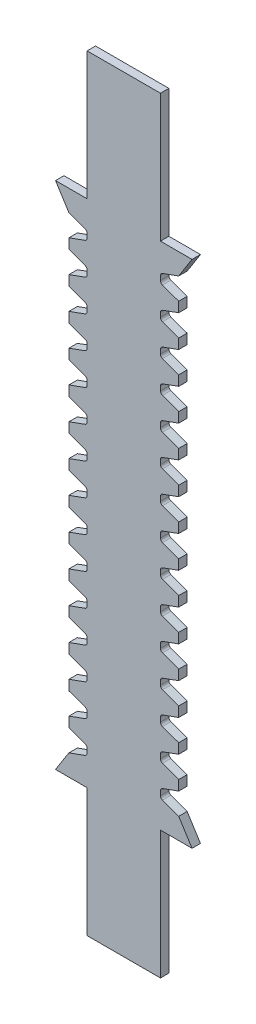
SolidWorks part; units mm, degrees
ref_plane "Front Plane" through (0, 0, 0) normal (0, 0, 1) x (1, 0, 0)
ref_plane "Top Plane" through (0, 0, 0) normal (0, 1, 0) x (1, 0, 0)
ref_plane "Right Plane" through (0, 0, 0) normal (1, 0, 0) x (0, 0, -1)
ref_axis "Axis1" through (0, -557.0644, 0) along (0, 1, 0)
sketch "SketchCI.m_strSketchName" plane through (0, 0, 0) normal (0, 0, 1) x (1, 0, 0)
  line L0 (-7.7057, 15.1301) -> (-7.7057, -438.7728)
  line L1 (-7.7057, -438.7728) -> (44.46, -438.7728)
  line L2 (44.46, -438.7728) -> (44.46, 15.1301)
  line L3 (44.46, 15.1301) -> (-7.7057, 15.1301)
  dimension "D1" = 7.7057
  dimension "D2" = 438.7728
  dimension "D3" = 44.46
  dimension "D4" = 15.1301
extrude "ExtrudeCI" add sketch "SketchCI.m_strSketchName" along normal blind 4 and the other way blind 4
sketch "SketchToothGeartrax1Gear" plane through (0, 0, 0) normal (0, 0, 1) x (1, 0, 0)
  line L0 (-7.7057, 10.3697) -> (-7.7057, -10.3697)
  line L1 (-7.7057, -10.3697) -> (7.7308, -4.7513)
  line L2 (9.6321, -2.0359) -> (9.6321, 2.0359)
  line L3 (7.7308, 4.7513) -> (-7.7057, 10.3697)
  arc A0 (7.7308, -4.7513) -> (9.6321, -2.0359) centre (6.7425, -2.0359) ccw
  arc A1 (9.6321, 2.0359) -> (7.7308, 4.7513) centre (6.7425, 2.0359) ccw
  dimension "D1" = 5.7793
  dimension "D2" = 5.7793
  dimension "ADDENDUM" = 7.7057
  dimension "FLANKONE" = 7.1088
  dimension "FLANKONEANGLE" = 70
  dimension "DEDENDUM" = 9.6321
  dimension "FLANKTWO" = 7.1088
  dimension "FLANKTWOANGLE" = 70
extrude "ToothExtrudeCutGeartrax1Gear" cut sketch "SketchToothGeartrax1Gear" against normal blind 4 and the other way blind 4
pattern_linear "PatternGeartrax1Gear" count 15 spacing 30.2602 along (0, -1, 0) of "ToothExtrudeCutGeartrax1Gear"
sketch "AuxiliarySketchGeartrax1Gear" plane through (0, 0, 0) normal (0, 0, 1) x (1, 0, 0)
  line L0 (0, 0) -> (0, -453.9029) construction
mirror "Mirror1" about plane through (44.46, -438.7728, -4) normal (1, 0, 0) of "ExtrudeCI", "ToothExtrudeCutGeartrax1Gear", "PatternGeartrax1Gear"
sketch "Sketch1" plane through (0, 0, 4) normal (0, 0, 1) x (1, 0, 0)
  line L0 (9.6321, 2.0359) -> (9.6321, 10.3697)
  line L1 (79.2879, 2.0359) -> (79.2879, 10.3697)
  line L2 (79.2879, 152.0359) -> (9.6321, 152.0359)
  line L3 (9.6321, 2.0359) -> (79.2879, 2.0359)
  line L4 (-7.7057, 10.3697) -> (-20.3679, 30.3697)
  line L5 (-20.3679, 30.3697) -> (9.6321, 30.3697)
  line L6 (-7.7057, 10.3697) -> (9.6321, 10.3697)
  line L7 (9.6321, 30.3697) -> (9.6321, 152.0359)
  line L8 (44.46, 152.0359) -> (44.46, 2.0359) construction
  line L9 (96.6257, 10.3697) -> (79.2879, 10.3697)
  line L10 (96.6257, 10.3697) -> (109.2879, 30.3697)
  line L11 (109.2879, 30.3697) -> (79.2879, 30.3697)
  line L12 (79.2879, 30.3697) -> (79.2879, 152.0359)
  line L13 (44.46, 15.1301) -> (44.46, -438.7728) construction
  line L14 (96.6257, 15.1301) -> (-7.7057, 15.1301) construction
  line L15 (-7.7057, -438.7728) -> (96.6257, -438.7728) construction
  line L16 (44.46, -211.8214) -> (79.2879, -211.8214) construction
  line L17 (79.2879, -213.8573) -> (79.2879, -209.7855) construction
  line L18 (9.6321, -425.6786) -> (9.6321, -434.0124)
  line L19 (-7.7057, -434.0124) -> (9.6321, -434.0124)
  line L20 (-20.3679, -454.0124) -> (9.6321, -454.0124)
  line L21 (-7.7057, -434.0124) -> (-20.3679, -454.0124)
  line L22 (9.6321, -454.0124) -> (9.6321, -575.6786)
  line L23 (79.2879, -575.6786) -> (9.6321, -575.6786)
  line L24 (79.2879, -454.0124) -> (79.2879, -575.6786)
  line L25 (9.6321, -425.6786) -> (79.2879, -425.6786)
  line L26 (79.2879, -425.6786) -> (79.2879, -434.0124)
  line L27 (96.6257, -434.0124) -> (79.2879, -434.0124)
  line L28 (109.2879, -454.0124) -> (79.2879, -454.0124)
  line L29 (96.6257, -434.0124) -> (109.2879, -454.0124)
  dimension "D1" = 150
  dimension "D2" = 20
  dimension "D3" = 30
extrude "Boss-Extrude1" add sketch "Sketch1" against normal blind 8
